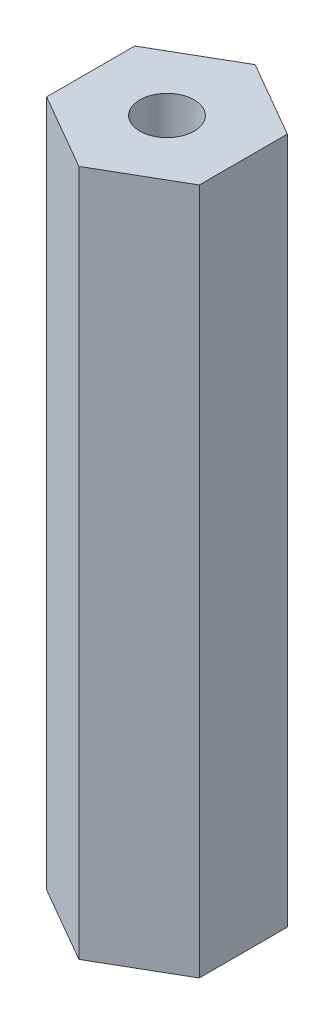
SolidWorks part; units mm, degrees
material "6061-T6 (SS)"
ref_plane "Front Plane" through (0, 0, 0) normal (0, 0, 1) x (1, 0, 0)
ref_plane "Top Plane" through (0, 0, 0) normal (0, 1, 0) x (1, 0, 0)
ref_plane "Right Plane" through (0, 0, 0) normal (1, 0, 0) x (0, 0, -1)
sketch "Sketch2" plane through (0, 0, 0) normal (0, 1, 0) x (1, 0, 0)
  line L1 (0, 3.6662) -> (-3.175, 1.8331)
  line L2 (-3.175, 1.8331) -> (-3.175, -1.8331)
  line L3 (-3.175, -1.8331) -> (0, -3.6662)
  line L4 (0, -3.6662) -> (3.175, -1.8331)
  line L5 (3.175, -1.8331) -> (3.175, 1.8331)
  line L6 (3.175, 1.8331) -> (0, 3.6662)
  circle A0 centre (0, 0) radius 3.175 construction
  dimension "D1" = 6.35
extrude "Boss-Extrude1" add sketch "Sketch2" along normal blind 28.575
hole_wizard "#4-40 Tapped Hole1" positions "Sketch4" profile "Sketch3" tap size "#4-40" standard "Ansi Inch" end condition through all
sketch "Sketch4" plane through (0, 28.575, 0) normal (0, 1, 0) x (-1, 0, 0)
  point P0 (0, 0)
sketch "Sketch3" plane through (0, 28.575, 0) normal (1, 0, 0) x (0, 0, 1)
  line L0 (0, 0) -> (0, 28.575)
  line L1 (0, 28.575) -> (1.1303, 28.575)
  line L2 (1.1303, 28.575) -> (1.1303, 0)
  line L5 (1.1303, 0) -> (0, 0)
  line L11 (0, -6.35) -> (0, 107.95) construction
  dimension "Thru Tap Drill Dia." = 2.2606
  dimension "Thru Tap Drill Depth" = 28.575
cosmetic thread "Hole Thread1"
